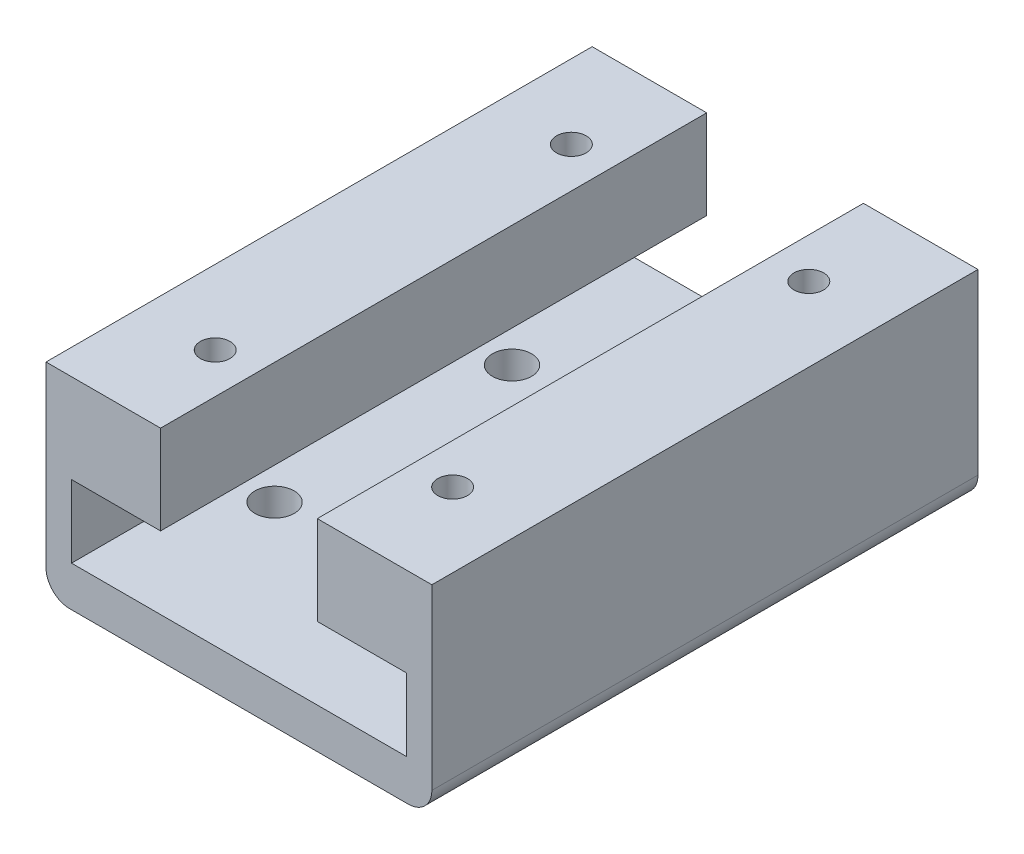
SolidWorks part; units mm, degrees
ref_plane "前视基准面" through (0, 0, 0) normal (0, 0, 1) x (1, 0, 0)
ref_plane "上视基准面" through (0, 0, 0) normal (0, 1, 0) x (1, 0, 0)
ref_plane "右视基准面" through (0, 0, 0) normal (1, 0, 0) x (0, 0, -1)
sketch "草图1" plane through (0, 0, 0) normal (0, 1, 0) x (1, 0, 0)
  line L1 (16.25, -23) -> (-16.25, -23)
  line L2 (16.25, -23) -> (16.25, 23)
  line L3 (16.25, 23) -> (-16.25, 23)
  line L4 (-16.25, -23) -> (-16.25, 23)
  line L5 (16.25, -23) -> (-16.25, 23) construction
  line L6 (16.25, 23) -> (-16.25, -23) construction
  point P0 (0, 0)
  dimension "D1" = 32.5
  dimension "D2" = 46
extrude "凸台-拉伸1" add sketch "草图1" along normal blind 17
sketch "草图2" plane through (0, 0, -23) normal (0, 0, -1) x (-1, 0, 0)
  line L0 (-16.25, 17) -> (16.25, 17) construction
  line L1 (-6.6, 9.5) -> (6.6, 9.5)
  line L2 (-6.6, 9.5) -> (-6.6, 17)
  line L3 (-6.6, 17) -> (6.6, 17)
  line L4 (6.6, 9.5) -> (6.6, 17)
  line L5 (-6.6, 9.5) -> (6.6, 17) construction
  line L6 (-6.6, 17) -> (6.6, 9.5) construction
  line L8 (-14.1, 3.4) -> (14.1, 3.4)
  line L9 (-14.1, 3.4) -> (-14.1, 9.5)
  line L10 (-14.1, 9.5) -> (14.1, 9.5)
  line L11 (14.1, 3.4) -> (14.1, 9.5)
  line L12 (-14.1, 3.4) -> (14.1, 9.5) construction
  line L13 (-14.1, 9.5) -> (14.1, 3.4) construction
  point P0 (0, 13.25)
  point P9 (0, 6.45)
  line M7 (16.25, 17) -> (-16.25, 17)
  dimension "D1" = 7.5
  dimension "D2" = 13.2
  dimension "D3" = 28.2
  dimension "D4" = 13.6
  dimension "D5" = 0
extrude "切除-拉伸2" cut sketch "草图2" against normal through all contours L1 L4 L2 M7 | L8 L11 L10 L1 L9 region at (0, 13.25, -23) region at (0, 6.45, -23)
sketch "草图4" plane through (0, 0, 0) normal (0, -1, 0) x (1, 0, 0)
  line L1 (-10, -10) -> (10, -10) construction
  line L2 (-10, -10) -> (-10, 10) construction
  line L3 (-10, 10) -> (10, 10) construction
  line L4 (10, -10) -> (10, 10) construction
  line L5 (-10, -10) -> (10, 10) construction
  line L6 (-10, 10) -> (10, -10) construction
  circle A0 centre (-10, 10) radius 1.65
  circle A1 centre (10, 10) radius 1.65
  circle A2 centre (10, -10) radius 1.65
  circle A3 centre (-10, -10) radius 1.65
  point P0 (0, 0)
  dimension "D3" = 3.3
  dimension "D4" = 3.3
  dimension "D5" = 3.3
  dimension "D6" = 3.3
  dimension "D1" = 20
  dimension "D2" = 20
extrude "切除-拉伸3" cut sketch "草图4" against normal up to next
sketch "草图5" plane through (0, 17, 0) normal (0, 1, 0) x (1, 0, 0)
  line L1 (-10, -15) -> (10, -15) construction
  line L2 (-10, -15) -> (-10, 15) construction
  line L3 (-10, 15) -> (10, 15) construction
  line L4 (10, -15) -> (10, 15) construction
  line L5 (-10, -15) -> (10, 15) construction
  line L6 (-10, 15) -> (10, -15) construction
  circle A0 centre (-10, 15) radius 1.25
  circle A1 centre (10, 15) radius 1.25
  circle A2 centre (10, -15) radius 1.25
  circle A3 centre (-10, -15) radius 1.25
  point P0 (0, 0)
  dimension "D3" = 2.5
  dimension "D4" = 2.5
  dimension "D5" = 2.5
  dimension "D6" = 2.5
  dimension "D1" = 30
  dimension "D2" = 20
extrude "切除-拉伸4" cut sketch "草图5" against normal blind 2
fillet "圆角1" radius 2 2 edges at (16.25, 0, 0) (-16.25, 0, 0)
equation "\"33.5.00mm\"=34"
